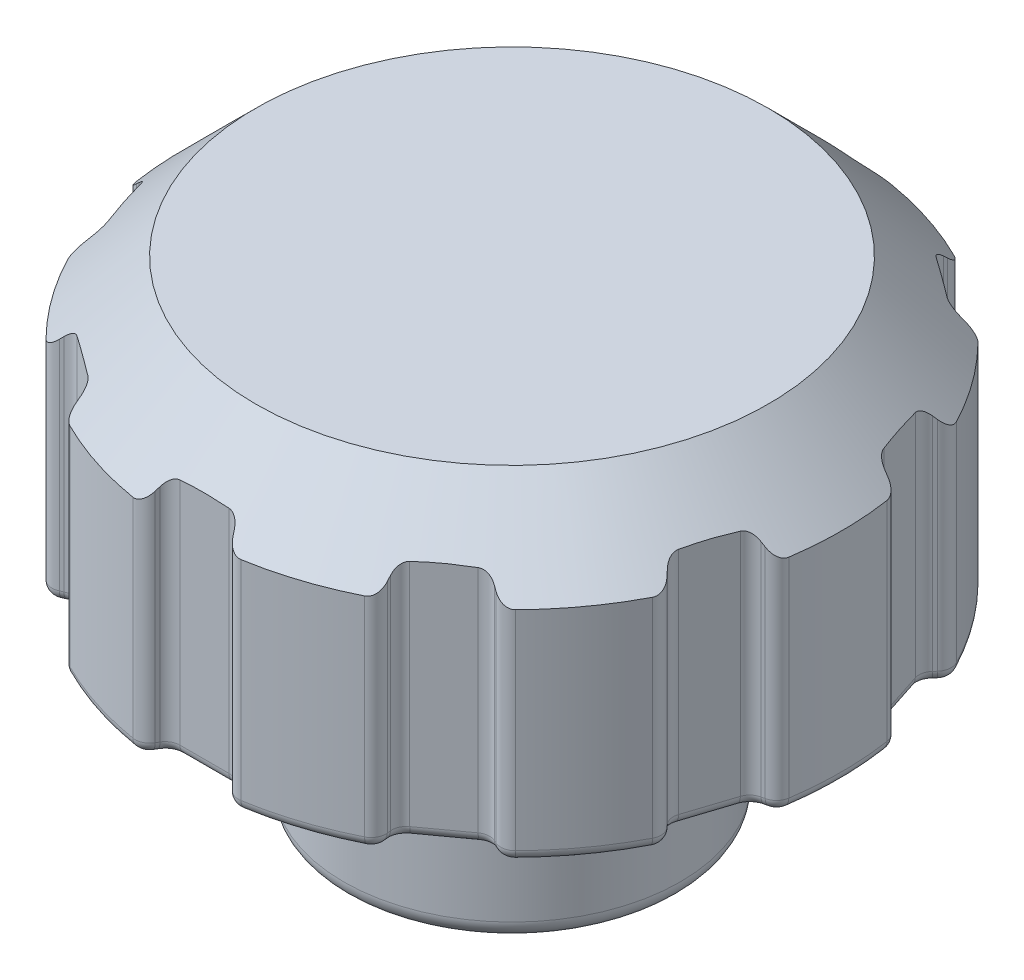
SolidWorks part; units mm, degrees
ref_plane "Ebene vorne" through (0, 0, 0) normal (0, 0, 1) x (1, 0, 0)
ref_plane "Ebene oben" through (0, 0, 0) normal (0, 1, 0) x (1, 0, 0)
ref_plane "Ebene rechts" through (0, 0, 0) normal (1, 0, 0) x (0, 0, -1)
ref_axis "Achse1" through (0, -5.65, 0) along (0, 1, 0)
sketch "Skizze1" plane through (0, 0, 0) normal (0, 1, 0) x (1, 0, 0)
  circle A0 centre (0, 0) radius 9
  dimension "D1" = 18
extrude "Aufsatz-Linear austragen1" add sketch "Skizze1" along normal blind 8
sketch "Skizze2" plane through (0, 0, 0) normal (0, -1, 0) x (1, 0, 0)
  circle A1 centre (0, 0) radius 4.6
  dimension "D1" = 9.2
extrude "Aufsatz-Linear austragen2" add sketch "Skizze2" along normal blind 5
sketch "Skizze3" plane through (0, -5, 0) normal (0, -1, 0) x (1, 0, 0)
  line L0 (1.2, -2.8583) -> (1.2, 2.8583)
  line L1 (0, 0) -> (1.2, 0) construction
  line L2 (0, 0) -> (-3.1, 0) construction
  circle A0 centre (0, 0) radius 3.1
  dimension "D2" = 6.2
  dimension "D1" = 4.3
extrude "Schnitt-Linear austragen2" cut sketch "Skizze3" against normal blind 6.5 contours L0 A0 region at (-0.6967, -5, 0)
fillet "Verrundung1" radius 2 1 edges at (0, 8, 9) profile chamfer
sketch "Skizze4" plane through (0, 8, 0) normal (0, 1, 0) x (1, 0, 0)
  line L0 (1.2, 8.9196) -> (0.9, 8.4)
  line L1 (0.9, 8.4) -> (-0.9, 8.4)
  line L2 (-0.9, 8.4) -> (-1.2, 8.9196)
  line L3 (0, 0) -> (0, 8.4) construction
  line L6 (0, 8.4) -> (0, 9) construction
  circle A0 centre (0, 0) radius 9 construction
  dimension "D1" = 60
  dimension "D2" = 2.4
  dimension "D3" = 0.6
extrude "Schnitt-Linear austragen3" cut sketch "Skizze4" against normal through all flip side to cut
pattern_circular "Kreismuster1" count 10 over 360 about axis through (0, -5.65, 0) along (0, 1, 0) of "Schnitt-Linear austragen3"
fillet "Verrundung2" radius 0.4 40 edges at (-1.2, 3, -8.9196) (-0.9, 3.276, -8.4) (1.2, 3, -8.9196) (0.9, 3.276, -8.4) (4.2093, 3.276, -7.3247) (4.272, 3, -7.9215) (-4.272, 3, -7.9215) (-4.2093, 3.276, -7.3247) (-5.6655, 3.276, -6.2667) (-6.2137, 3, -6.5108) (-8.1123, 3, -3.8976) (-7.7108, 3.276, -3.4517) (-8.267, 3.276, -1.7398) (-8.8539, 3, -1.6151) (-8.8539, 3, 1.6151) (-8.267, 3.276, 1.7398) (-7.7108, 3.276, 3.4517) (-8.1123, 3, 3.8976) (-6.2137, 3, 6.5108) (-5.6655, 3.276, 6.2667) (-4.2093, 3.276, 7.3247) (-4.272, 3, 7.9215) (-1.2, 3, 8.9196) (-0.9, 3.276, 8.4) (0.9, 3.276, 8.4) (1.2, 3, 8.9196) (4.272, 3, 7.9215) (4.2093, 3.276, 7.3247) (5.6655, 3.276, 6.2667) (6.2137, 3, 6.5108) (8.1123, 3, 3.8976) (7.7108, 3.276, 3.4517) (8.267, 3.276, 1.7398) (8.8539, 3, 1.6151) (8.8539, 3, -1.6151) (8.267, 3.276, -1.7398) (7.7108, 3.276, -3.4517) (8.1123, 3, -3.8976) (6.2137, 3, -6.5108) (5.6655, 3.276, -6.2667)
fillet "Verrundung3" radius 0.3 81 edges at (1.2393, 0, -8.8453) (1.0396, 0, -8.6418) (0.869, 0, -8.4536) (0, 0, -8.4) (-0.869, 0, -8.4536) (-1.0396, 0, -8.6418) (-1.2393, 0, -8.8453) (-2.7812, 0, -8.5595) (-4.1965, 0, -7.8844) (-4.2385, 0, -7.6024) (-4.2658, 0, -7.3499) (-4.9374, 0, -6.7957) (-5.672, 0, -6.3283) (-5.9206, 0, -6.3803) (-6.2018, 0, -6.4275) (-7.2812, 0, -5.2901) (-8.0294, 0, -3.912) (-7.8976, 0, -3.6592) (-7.7713, 0, -3.4388) (-7.9889, 0, -2.5957) (-8.3084, 0, -1.7858) (-8.5401, 0, -1.6818) (-8.7953, 0, -1.5547) (-9, 0, 0) (-8.7953, 0, 1.5547) (-8.5401, 0, 1.6818) (-8.3084, 0, 1.7858) (-7.9889, 0, 2.5957) (-7.7713, 0, 3.4388) (-7.8976, 0, 3.6592) (-8.0294, 0, 3.912) (-7.2812, 0, 5.2901) (-6.2018, 0, 6.4275) (-5.9206, 0, 6.3803) (-5.672, 0, 6.3283) (-4.9374, 0, 6.7957) (-4.2658, 0, 7.3499) (-4.2385, 0, 7.6024) (-4.1965, 0, 7.8844) (-2.7812, 0, 8.5595) (-1.2393, 0, 8.8453) (-1.0396, 0, 8.6418) (-0.869, 0, 8.4536) (0, 0, 8.4) (0.869, 0, 8.4536) (1.0396, 0, 8.6418) (1.2393, 0, 8.8453) (2.7812, 0, 8.5595) (4.1965, 0, 7.8844) (4.2385, 0, 7.6024) (4.2658, 0, 7.3499) (4.9374, 0, 6.7957) (5.672, 0, 6.3283) (5.9206, 0, 6.3803) (6.2018, 0, 6.4275) (7.2812, 0, 5.2901) (8.0294, 0, 3.912) (7.8976, 0, 3.6592) (7.7713, 0, 3.4388) (7.9889, 0, 2.5957) (8.3084, 0, 1.7858) (8.5401, 0, 1.6818) (8.7953, 0, 1.5547) (9, 0, 0) (8.7953, 0, -1.5547) (8.5401, 0, -1.6818) (8.3084, 0, -1.7858) (7.9889, 0, -2.5957) (7.7713, 0, -3.4388) (7.8976, 0, -3.6592) (8.0294, 0, -3.912) (7.2812, 0, -5.2901) (6.2018, 0, -6.4275) (5.9206, 0, -6.3803) (5.672, 0, -6.3283) (4.9374, 0, -6.7957) (4.2658, 0, -7.3499) (4.2385, 0, -7.6024) (4.1965, 0, -7.8844) (2.7812, 0, -8.5595) (0, 0, -4.6)
fillet "Verrundung4" radius 0.5 1 edges at (0, -5, -4.6)
chamfer "Fase1" distance 0.7 angle 45 2 edges at (1.2, -5, 0) (-3.1, -5, 0)
